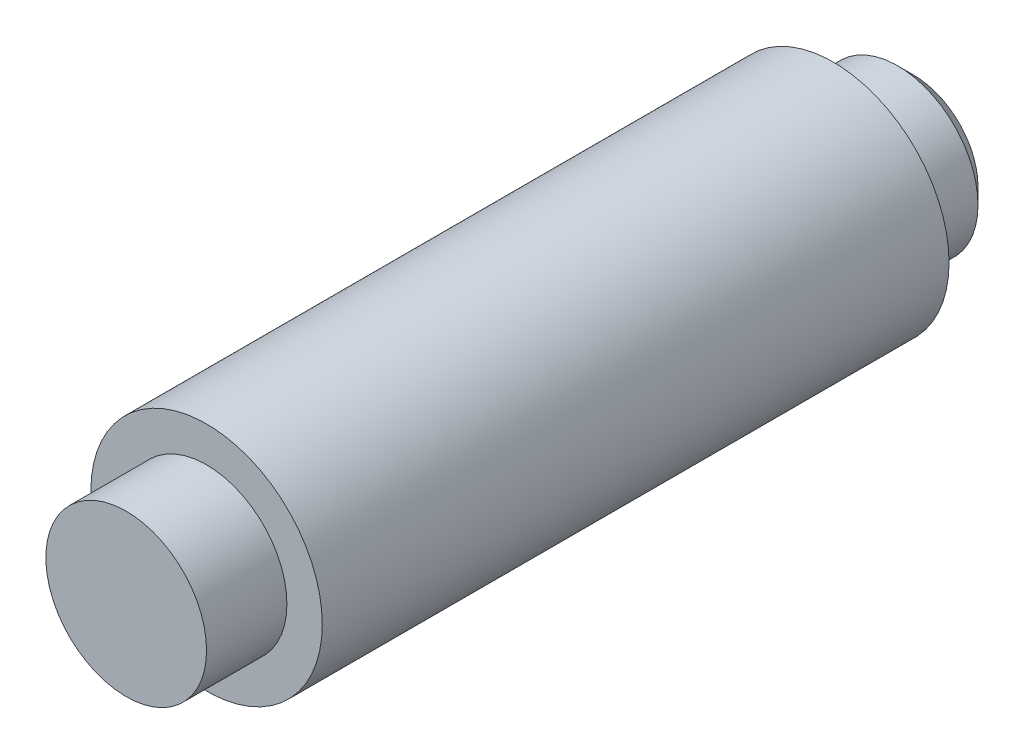
SolidWorks part; units mm, degrees
ref_plane "Front Plane" through (0, 0, 0) normal (0, 0, 1) x (1, 0, 0)
ref_plane "Top Plane" through (0, 0, 0) normal (0, 1, 0) x (1, 0, 0)
ref_plane "Right Plane" through (0, 0, 0) normal (1, 0, 0) x (0, 0, -1)
sketch "Sketch2" plane through (0, 0, 0) normal (0, 0, 1) x (1, 0, 0)
  circle A0 centre (0, 0) radius 1.25
  dimension "D1" = 2.5
sketch "Sketch3" plane through (0, 0, 0) normal (0, 0, 1) x (1, 0, 0)
  line L5 (-3.6, 3.6) -> (3.6, 3.6) construction
  line L6 (-3.6, 3.6) -> (-3.6, -3.6) construction
  line L7 (-3.6, -3.6) -> (3.6, -3.6) construction
  line L8 (3.6, 3.6) -> (3.6, -3.6) construction
  circle A0 centre (0, 0) radius 3.6
  point P4 (0, 3.6)
  point P6 (-3.6, 0)
  dimension "D1" = 7.2
extrude "Boss-Extrude1" add sketch "Sketch3" along normal blind 19.5
sketch "Sketch4" plane through (0, 0, 0) normal (0, 0, 1) x (1, 0, 0)
  circle A0 centre (0, 0) radius 2.5
  dimension "D1" = 5
extrude "Boss-Extrude2" add sketch "Sketch4" against normal blind 2.5
sketch "Sketch5" plane through (0, 0, 19.5) normal (0, 0, 1) x (1, 0, 0)
  circle A0 centre (0, 0) radius 2.5
  dimension "D1" = 5
extrude "Boss-Extrude3" add sketch "Sketch5" along normal blind 2.5
chamfer "Chamfer1" distance 0.5 angle 45 1 edges at (2.5, 0, -2.5)
equation "\"length\"=19.5"
equation "\"D1@Boss-Extrude1\"=\"length\""
